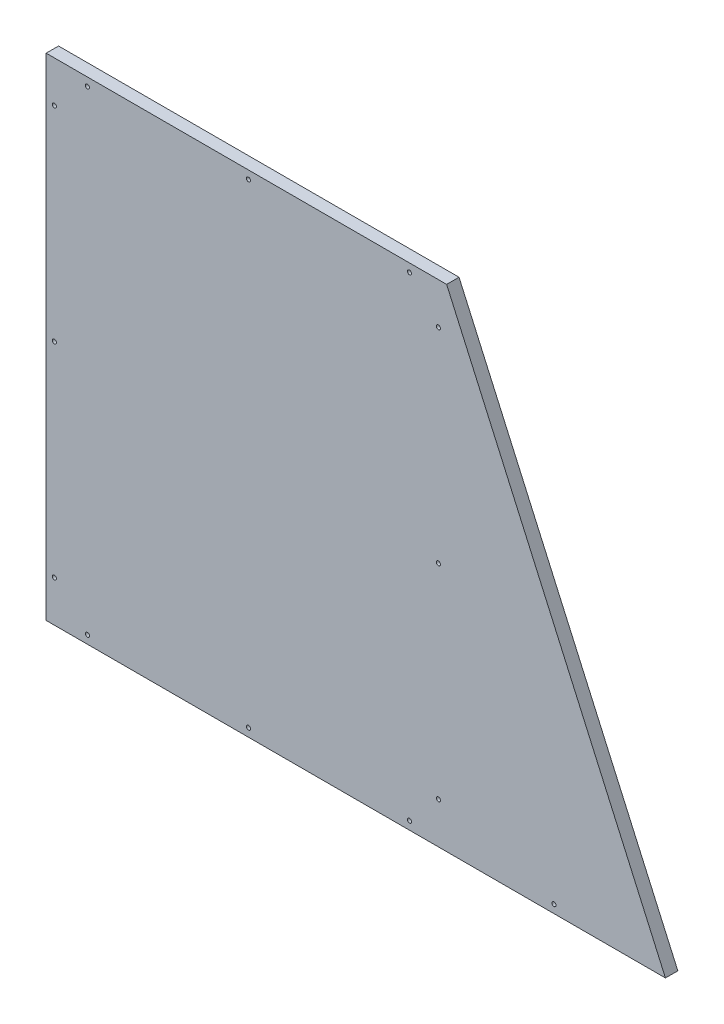
SolidWorks part; units mm, degrees
material "西洋杉"
ref_plane "正面" through (0, 0, 0) normal (0, 0, 1) x (1, 0, 0)
ref_plane "平面" through (0, 0, 0) normal (0, 1, 0) x (1, 0, 0)
ref_plane "右側面" through (0, 0, 0) normal (1, 0, 0) x (0, 0, -1)
sketch "ｽｹｯﾁ1" plane through (0, 0, 0) normal (0, 0, 1) x (1, 0, 0)
  line L0 (0, 297.5) -> (0, -297.5) construction
  line L1 (-242.5, 297.5) -> (242.5, 297.5)
  line L2 (-242.5, 297.5) -> (-242.5, -297.5)
  line L3 (-242.5, -297.5) -> (507.5, -297.5)
  line L4 (242.5, 297.5) -> (507.5, -297.5)
  line L5 (-242.5, 297.5) -> (507.5, -297.5) construction
  line L6 (-242.5, -297.5) -> (242.5, 297.5) construction
  line L7 (-242.5, 0) -> (375, 0) construction
  point P0 (203.975, -56.7035)
  point P8 (-16.9855, 72.9459)
  point P11 (94.867, 67.8495)
  dimension "D1" = 595
  dimension "D2" = 485
  dimension "D3" = 750
extrude "ﾎﾞｽ - 押し出し1" add sketch "ｽｹｯﾁ1" along normal blind 15
sketch "ｽｹｯﾁ2" plane through (0, 0, 15) normal (0, 0, 1) x (1, 0, 0)
  line L0 (-232.5, 297.5) -> (-232.5, -297.5) construction
  line L1 (242.5, 297.5) -> (-242.5, 297.5) construction
  line L2 (-242.5, -297.5) -> (507.5, -297.5) construction
  line L3 (-242.5, 297.5) -> (-242.5, -297.5) construction
  line L4 (-242.5, 287.5) -> (246.9538, 287.5) construction
  line L5 (507.5, -297.5) -> (242.5, 297.5) construction
  circle A0 centre (-232.5, 247.5) radius 2.5
  circle A1 centre (-232.5, 0) radius 2.5
  circle A2 centre (-232.5, -247.5) radius 2.5
  circle A3 centre (-192.5, 287.5) radius 2.5
  circle A4 centre (2.5, 287.5) radius 2.5
  circle A5 centre (197.5, 287.5) radius 2.5
  circle A6 centre (392.5, 287.5) radius 2.5
  dimension "D7" = 5
  dimension "D1" = 10
  dimension "D3" = 50
  dimension "D5" = 10
  dimension "D6" = 489.4538
  dimension "D8" = 50
  dimension "D10" = 595
  dimension "D11" = 247.5
  dimension "D4" = 3
  dimension "D9" = 4
extrude "ｶｯﾄ - 押し出し1" cut sketch "ｽｹｯﾁ2" against normal through all contours A3 | A4 | A5
extrude "ｶｯﾄ - 押し出し2" cut sketch "ｽｹｯﾁ2<3>" against normal through all contours A0 | A1 | A2
sketch "ｽｹｯﾁ2<3>" plane through (0, 0, 15) normal (0, 0, 1) x (1, 0, 0) same geometry as "ｽｹｯﾁ2"
mirror "ﾐﾗｰ1" about plane through (0, 0, 0) normal (0, 1, 0) of "ｶｯﾄ - 押し出し1"
mirror "ﾐﾗｰ2" about plane through (0, 0, 0) normal (1, 0, 0) of "ｶｯﾄ - 押し出し2"
sketch "ｽｹｯﾁ4" plane through (0, 0, 15) normal (0, 0, 1) x (1, 0, 0)
  line L0 (-242.5, -297.5) -> (507.5, -297.5) construction
  circle A0 centre (372.5, -287.5) radius 2.5
  circle A1 centre (197.5, -287.5) radius 2.5 construction
  dimension "D1" = 5
  dimension "D2" = 175
  dimension "D3" = 10
extrude "ｶｯﾄ - 押し出し3" cut sketch "ｽｹｯﾁ4" against normal through all
equation "\"D11@ｽｹｯﾁ2\"=495/2"
equation "\"D3@ｽｹｯﾁ6\"=\"D2@ｽｹｯﾁ6\""
